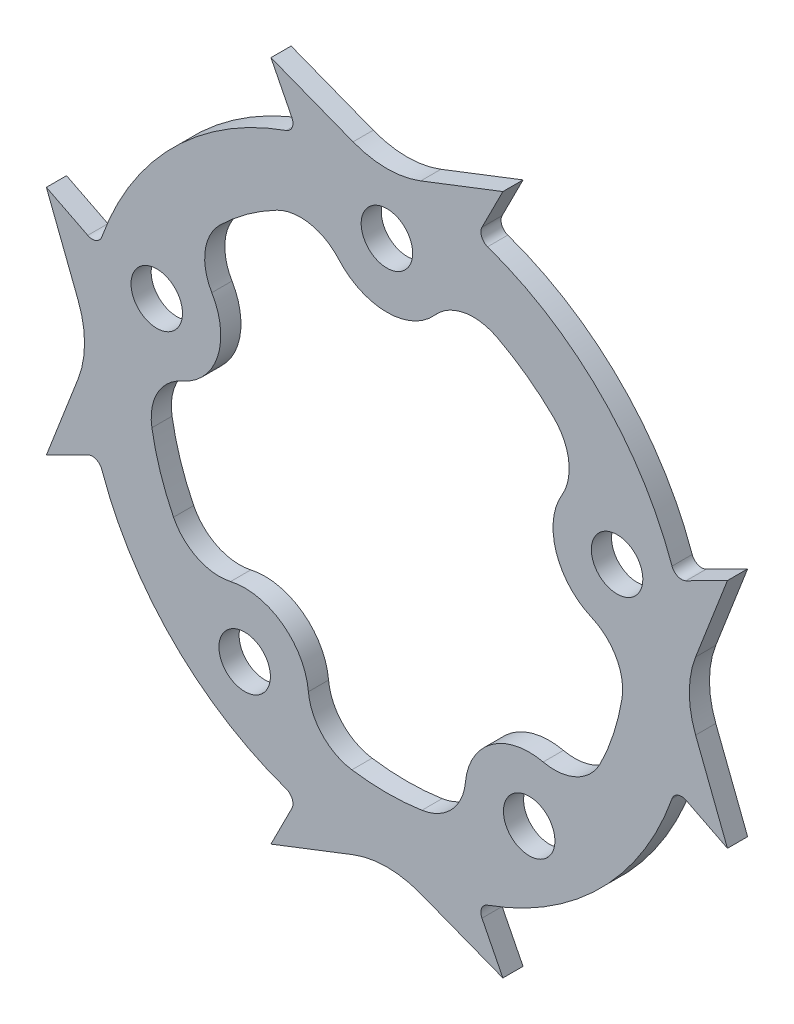
SolidWorks part; units mm, degrees
ref_plane "Front Plane" through (0, 0, 0) normal (0, 0, 1) x (1, 0, 0)
ref_plane "Top Plane" through (0, 0, 0) normal (0, 1, 0) x (1, 0, 0)
ref_plane "Right Plane" through (0, 0, 0) normal (1, 0, 0) x (0, 0, -1)
sketch "Sketch1" plane through (0, 0, 0) normal (0, 0, 1) x (1, 0, 0)
  line L0 (0, 24) -> (0, 0) construction
  line L1 (0, -23.6347) -> (0, -29.9847) construction
  line L2 (0, 0) -> (-11.5, 33.7706) construction
  line L3 (-11.5, 33.7706) -> (-8.9038, 28.6322)
  line L4 (-11.5, 33.7706) -> (-3.3557, 30.6125)
  line L5 (-11.5, 33.7706) -> (-3.7663, 36.4042) construction
  line L6 (0, 0) -> (0, 35.675) construction
  line L7 (11.5, 33.7706) -> (3.3557, 30.6125)
  line L8 (11.5, 33.7706) -> (8.9038, 28.6322)
  line L9 (-9.6657, 28.3841) -> (47321.284, 16146.1136) construction
  circle A0 centre (0, 0) radius 29.9847
  circle A1 centre (0, 24) radius 2.5527
  arc A2 (4.7678, 19.8059) -> (-4.7678, 19.8059) centre (0, 24) cw
  arc A3 (-23.3071, -3.9214) -> (-21.1608, -10.5271) centre (0, 0) ccw
  arc A4 (4.7678, 19.8059) -> (10.9318, 20.9546) centre (8.5821, 16.4507) cw
  arc A5 (-4.7678, 19.8059) -> (-10.9318, 20.9546) centre (-8.5821, 16.4507) ccw
  arc A6 (20.3099, 1.5859) -> (17.3632, 10.6548) centre (22.8254, 7.4164) cw
  circle A7 centre (22.8254, 7.4164) radius 2.5527
  arc A8 (17.3632, 10.6548) -> (16.5509, 16.872) centre (12.9935, 13.2456) ccw
  arc A9 (20.3099, 1.5859) -> (23.3071, -3.9214) centre (18.2975, -3.0785) cw
  arc A10 (7.7844, -18.8258) -> (15.4989, -13.2209) centre (14.1068, -19.4164) cw
  circle A11 centre (14.1068, -19.4164) radius 2.5527
  arc A12 (15.4989, -13.2209) -> (21.1608, -10.5271) centre (16.6125, -8.2644) ccw
  arc A13 (7.7844, -18.8258) -> (3.4728, -23.3782) centre (2.7264, -18.3533) cw
  arc A14 (-15.4989, -13.2209) -> (-7.7844, -18.8258) centre (-14.1068, -19.4164) cw
  circle A15 centre (-14.1068, -19.4164) radius 2.5527
  arc A16 (-7.7844, -18.8258) -> (-3.4728, -23.3782) centre (-2.7264, -18.3533) ccw
  arc A17 (-15.4989, -13.2209) -> (-21.1608, -10.5271) centre (-16.6125, -8.2644) cw
  arc A18 (-17.3632, 10.6548) -> (-20.3099, 1.5859) centre (-22.8254, 7.4164) cw
  circle A19 centre (-22.8254, 7.4164) radius 2.5527
  arc A20 (-20.3099, 1.5859) -> (-23.3071, -3.9214) centre (-18.2975, -3.0785) ccw
  arc A21 (-17.3632, 10.6548) -> (-16.5509, 16.872) centre (-12.9935, 13.2456) cw
  arc A22 (-3.4728, -23.3782) -> (3.4728, -23.3782) centre (0, 0) ccw
  arc A23 (21.1608, -10.5271) -> (23.3071, -3.9214) centre (0, 0) ccw
  arc A24 (16.5509, 16.872) -> (10.9318, 20.9546) centre (0, 0) ccw
  arc A25 (-10.9318, 20.9546) -> (-16.5509, 16.872) centre (0, 0) ccw
  circle A26 centre (0, 0) radius 35.675 construction
  arc A27 (-3.3557, 30.6125) -> (0, 29.9847) centre (0, 39.2664) ccw
  arc A29 (3.3557, 30.6125) -> (0, 29.9847) centre (0, 39.2664) cw
  dimension "D2" = 5.1054
  dimension "D4" = 5.08
  dimension "D5" = 6.35
  dimension "D6" = 24
  dimension "D3" = 6.35
  dimension "D8" = 71.35
  dimension "D12" = 59.9694
  dimension "D9" = 8
  dimension "D10" = 40
  dimension "D11" = 23
  dimension "D7" = 5
extrude "Boss-Extrude1" add sketch "Sketch1" along normal blind 2 contours A0 A25 A5 A2 A4 A24 A8 A6 A9 A23 A12 A10 A13 A22 A16 A14 A17 A3 A20 A18 A21 A19 A15 A11 A7 A1 region at (-4.3756, 28.8062, 0)
extrude "Boss-Extrude2" add sketch "Sketch1<4>" along normal up to surface (2 mm away) contours A27 L4 L3 A0 | L7 A29 A0 L8 region at (-7.4005, 30.8552, 0) region at (7.4005, 30.8552, 0) up to face at (0, 0, 2)
sketch "Sketch1<4>" plane through (0, 0, 0) normal (0, 0, 1) x (1, 0, 0) same geometry as "Sketch1"
fillet "Fillet1" radius 1 2 edges at (8.9038, 28.6322, 1) (-8.9038, 28.6322, 1)
pattern_circular "CirPattern1" count 4 over 360 about axis through (0, 0, 2) along (0, 0, 1) of "Fillet1", "Boss-Extrude2"
